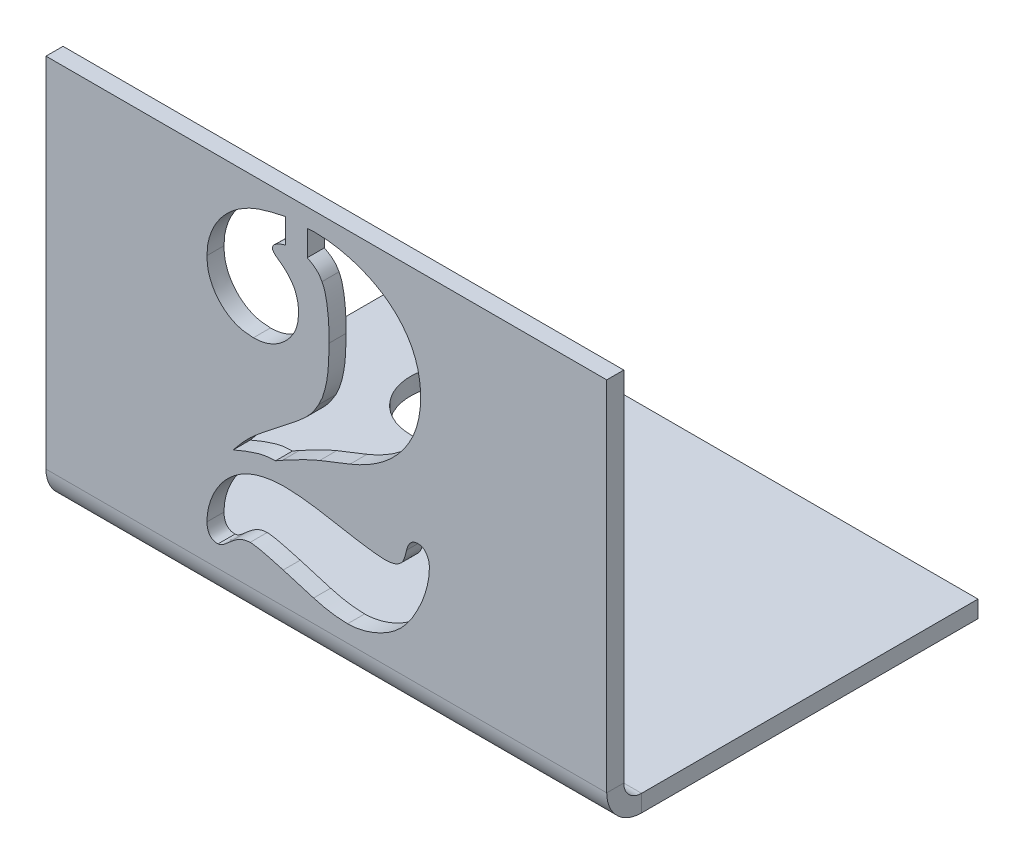
SolidWorks part; units mm, degrees
note: The reader was unsure of these and kept them because the rebuilt part matched: flange length of "Edge-Flange1".
material "16 Ga. SHEET METAL"
ref_plane "Front Plane" through (0, 0, 0) normal (0, 0, 1) x (1, 0, 0)
ref_plane "Top Plane" through (0, 0, 0) normal (0, 1, 0) x (1, 0, 0)
ref_plane "Right Plane" through (0, 0, 0) normal (1, 0, 0) x (0, 0, -1)
sketch "Sketch1" plane through (0, 0, 0) normal (0, 1, 0) x (1, 0, 0)
  line L1 (-25, 0) -> (25, 0)
  line L2 (-25, 0) -> (-25, 30)
  line L3 (-25, 30) -> (25, 30)
  line L4 (25, 0) -> (25, 30)
  dimension "D1" = 30
  dimension "D2" = 50
base flange "Base-Flange1" sketch "Sketch1" thickness 1.5189 reverse thickness direction yes parameters "D1"=1.5875
edge flange "Edge-Flange1" sketch "Sketch8" flange angle 90 flange length 35 flange position bend outside bend radius 1.5875 thickness 1.5189 relief rectangular parameters "D6"=10
sketch "Sketch8" plane through (0, 1.5189, 0) normal (0, 0, 1) x (1, 0, 0)
  line L0 (-25, 0) -> (25, 0) construction
  line L1 (-25, 0) -> (25, 0)
  line L2 (-25, 0) -> (-25, 33.4811)
  line L3 (-25, 33.4811) -> (25, 33.4811)
  line L4 (25, 33.4811) -> (25, 0)
bend "EdgeBend1" bend radius 1.5875 bend angle 90 parameters "D5"=1
hole_wizard "M8 Clearance Hole1" positions "Sketch9" profile "Sketch10" hole size "M8" standard "Peddi DIN" end condition through all
sketch "Sketch9" plane through (0, 1.5189, 0) normal (0, 1, 0) x (1, 0, 0)
  line L0 (25, -3.1064) -> (-25, -3.1064) construction
  line L1 (-25, 30) -> (-25, 0) construction
  point P0 (-13, 21.8936)
  dimension "D1" = 25
  dimension "D2" = 12
sketch "Sketch10" plane through (-13, 1.5189, -21.8936) normal (1, 0, 0) x (0, 0, 1)
  line L0 (0, 0) -> (0, 1.5189)
  line L1 (0, 1.5189) -> (4.5, 1.5189)
  line L2 (4.5, 1.5189) -> (4.5, 0)
  line L5 (4.5, 0) -> (0, 0)
  line L11 (0, -6.35) -> (0, 107.95) construction
  dimension "Thru Hole Dia." = 9
  dimension "Thru Hole Depth" = 1.5189
sketch "Sketch11" plane through (0, 0, 3.1064) normal (0, 0, 1) x (1, 0, 0)
  line L0 (-25, 0) -> (25, 0) construction
  text T0 "2\r\n" font "Stencil" height 28
  dimension "D1" = 5
extrude "Cut-Extrude1" cut sketch "Sketch11" against normal through all
other "Freeze***"
sketch "Bend-Lines1" [suppressed] plane through (0, 0, 0) normal (0, 1, 0) x (1, 0, 0)
sketch "Bounding-Box1" [suppressed] plane through (0, 0, 0) normal (0, 1, 0) x (1, 0, 0)
sheet metal parameters "Sheet-Metal1" thickness 1.5189 parameters "D1"=1.5875
flat pattern "Flat-Pattern1" [suppressed]
sketch "Bend-Lines2" plane through (0, 0, 0) normal (0, 1, 0) x (1, 0, 0)
sketch "Bounding-Box2" [suppressed] plane through (0, 0, 0) normal (0, 1, 0) x (1, 0, 0)
sheet metal parameters "Sheet-Metal2" thickness 1.5189 parameters "D1"=1.5875
flat pattern "Flat-Pattern1" [suppressed]
sketch "Bend-Lines2" plane through (0, 0, 0) normal (0, 1, 0) x (1, 0, 0)
sketch "Bounding-Box2" [suppressed] plane through (0, 0, 0) normal (0, 1, 0) x (1, 0, 0)
bend of the flat pattern "Flatten-<EdgeBend1>1"
sheet metal parameters "Sheet-Metal3" thickness 1.5189 parameters "D1"=1.5875
flat pattern "Flat-Pattern1" [suppressed]
sketch "Bend-Lines2" plane through (0, 0, 0) normal (0, 1, 0) x (1, 0, 0)
sketch "Bounding-Box2" [suppressed] plane through (0, 0, 0) normal (0, 1, 0) x (1, 0, 0)
bend of the flat pattern "Flatten-<EdgeBend1>1"
sheet metal parameters "Sheet-Metal4" thickness 1.5189 parameters "D1"=1.5875
flat pattern "Flat-Pattern1"
sketch "Bend-Lines2" plane through (0, 0, 0) normal (0, -1, 0) x (-1, 0, 0)
  line L0 (-25, -1.724) -> (25, -1.724) construction
  line L1 (-25, -1.724) -> (25, -1.724) construction
sketch3d "Bounding-Box2" [suppressed]
  line L0 (25, -35.3416, 0) -> (25, 30, 0) construction
  line L1 (-25, -35.3416, 0) -> (-25, 30, 0) construction
  line L2 (25, -35.3416, 0) -> (-25, -35.3416, 0) construction
  line L3 (25, 30, 0) -> (-25, 30, 0) construction
bend of the flat pattern "Flatten-<EdgeBend1>1"
